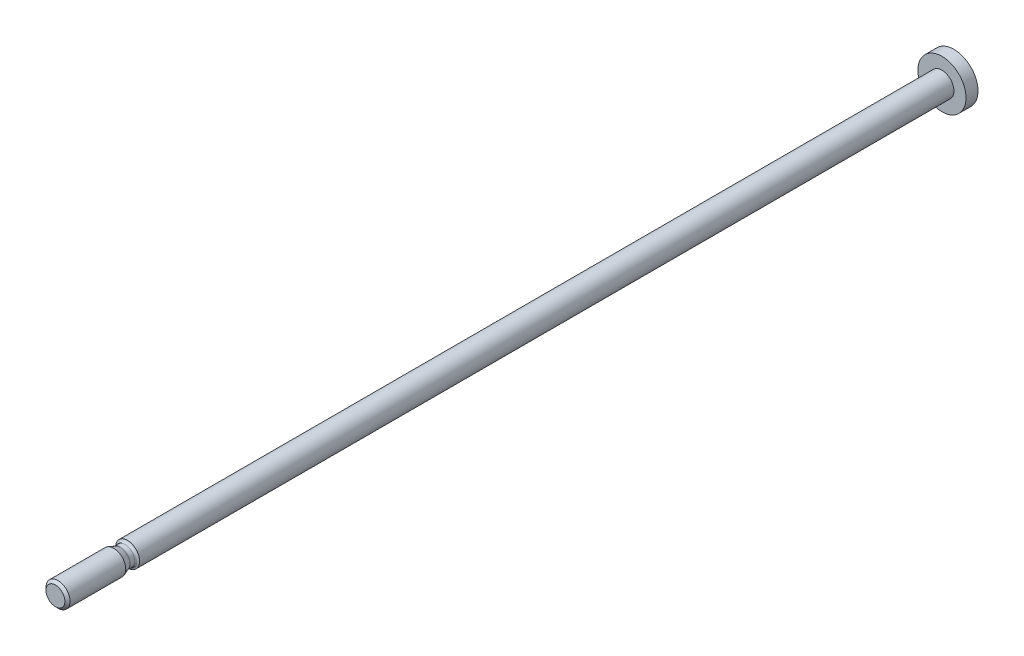
SolidWorks part; units mm, degrees
ref_plane "Ebene vorne" through (0, 0, 0) normal (0, 0, 1) x (1, 0, 0)
ref_plane "Ebene oben" through (0, 0, 0) normal (0, 1, 0) x (1, 0, 0)
ref_plane "Ebene rechts" through (0, 0, 0) normal (1, 0, 0) x (0, 0, -1)
sketch "Skizze1" plane through (0, 0, 0) normal (1, 0, 0) x (0, 0, -1)
  line L0 (-4, 0) -> (-4, 2)
  line L1 (-4, 2) -> (131.5, 2)
  line L2 (131.5, 2) -> (131.5, 4)
  line L3 (131.5, 4) -> (133.5, 4)
  line L4 (133.5, 4) -> (133.5, 0)
  line L5 (133.5, 0) -> (-4, 0)
  line L6 (133.5, 0) -> (-4, 0) construction
revolve "Rotation1" add sketch "Skizze1" angle 360 about L6 reverse direction yes
sketch "Skizze2" plane through (0, 0, 0) normal (1, 0, 0) x (0, 0, -1)
  line L0 (-16, 0) -> (-16, 1.5705)
  line L1 (-16, 1.5705) -> (-15.5705, 2)
  line L2 (-15.5705, 2) -> (-6.299, 2)
  line L3 (-6.299, 2) -> (-5.2663, 1.6241)
  line L4 (-5.1295, 1.6) -> (-4.4, 1.6)
  line L5 (-4, 2) -> (-3, 2)
  line L6 (-3, 2) -> (-3, 0)
  line L7 (-3, 0) -> (-16, 0)
  line L8 (-3, 0) -> (-16, 0) construction
  arc A0 (-5.2663, 1.6241) -> (-5.1295, 1.6) centre (-5.1295, 2) ccw
  arc A1 (-4.4, 1.6) -> (-4, 2) centre (-4.4, 2) ccw
revolve "Rotation2" add sketch "Skizze2" angle 360 about L8 reverse direction yes
cosmetic thread "Gewindedarstellung1"
ref_plane "Ebene1" through (0, 0, 4) normal (0, 0, 1) x (1, 0, 0)
ref_plane "Ebene2" through (0, 0, -274) normal (0, 0, 1) x (1, 0, 0)
ref_plane "Ebene3" through (0, 0, 12) normal (0, 0, 1) x (1, 0, 0)
ref_plane "Ebene4" through (0, 0, 8.2) normal (0, 0, 1) x (1, 0, 0)
ref_plane "FDT_KSAUFSATZ XY" through (0, 0, 8.2) normal (0, 0, 1) x (1, 0, 0)
ref_plane "FDT_KSAUFSATZ XZ" through (0, 0, 0) normal (0, 1, 0) x (1, 0, 0)
ref_plane "FDT_KSAUFSATZ YZ" through (0, 0, 0) normal (-1, 0, 0) x (0, 0, 1)
ref_axis "FDT_KSAUFSATZ X" through (80.9, 0, 8.2) along (-1, 0, 0)
ref_axis "FDT_KSAUFSATZ Y" through (0, 50, 8.2) along (0, -1, 0)
ref_axis "FDT_KSAUFSATZ Z" through (0, 0, 80.9) along (0, 0, -1)
sketch3d "FDT_KSAUFSATZ"
  point P0 (0, 0, 8.2)
ref_plane "FDT_NUT XY" through (0, 0, 8.2) normal (0, 0, 1) x (1, 0, 0)
ref_plane "FDT_NUT XZ" through (0, 0, 0) normal (0, 1, 0) x (1, 0, 0)
ref_plane "FDT_NUT YZ" through (0, 0, 0) normal (-1, 0, 0) x (0, 0, 1)
ref_axis "FDT_NUT X" through (80.9, 0, 8.2) along (-1, 0, 0)
ref_axis "FDT_NUT Y" through (0, 50, 8.2) along (0, -1, 0)
ref_axis "FDT_NUT Z" through (0, 0, 80.9) along (0, 0, -1)
sketch3d "FDT_NUT"
  point P0 (0, 0, 8.2)
ref_plane "KS XY" through (0, 0, 0) normal (0, 0, -1) x (-1, 0, 0)
ref_plane "KS XZ" through (0, 0, 0) normal (0, 1, 0) x (1, 0, 0)
ref_plane "KS YZ" through (0, 0, 0) normal (1, 0, 0) x (0, 0, -1)
ref_axis "KS X" through (-80.9, 0, 0) along (1, 0, 0)
ref_axis "KS Y" through (0, 50, 0) along (0, -1, 0)
ref_axis "KS Z" through (0, 0, -80.9) along (0, 0, 1)
sketch3d "KS"
  point P0 (0, 0, 0)
ref_plane "NUT1 XY" through (0, 0, 12) normal (0, 0, 1) x (1, 0, 0)
ref_plane "NUT1 XZ" through (0, 0, 0) normal (0, -1, 0) x (-1, 0, 0)
ref_plane "NUT1 YZ" through (0, 0, 0) normal (1, 0, 0) x (0, 0, -1)
ref_axis "NUT1 X" through (-80.9, 0, 12) along (1, 0, 0)
ref_axis "NUT1 Y" through (0, -50, 12) along (0, 1, 0)
ref_axis "NUT1 Z" through (0, 0, 80.9) along (0, 0, -1)
sketch3d "NUT1"
  point P0 (0, 0, 12)
